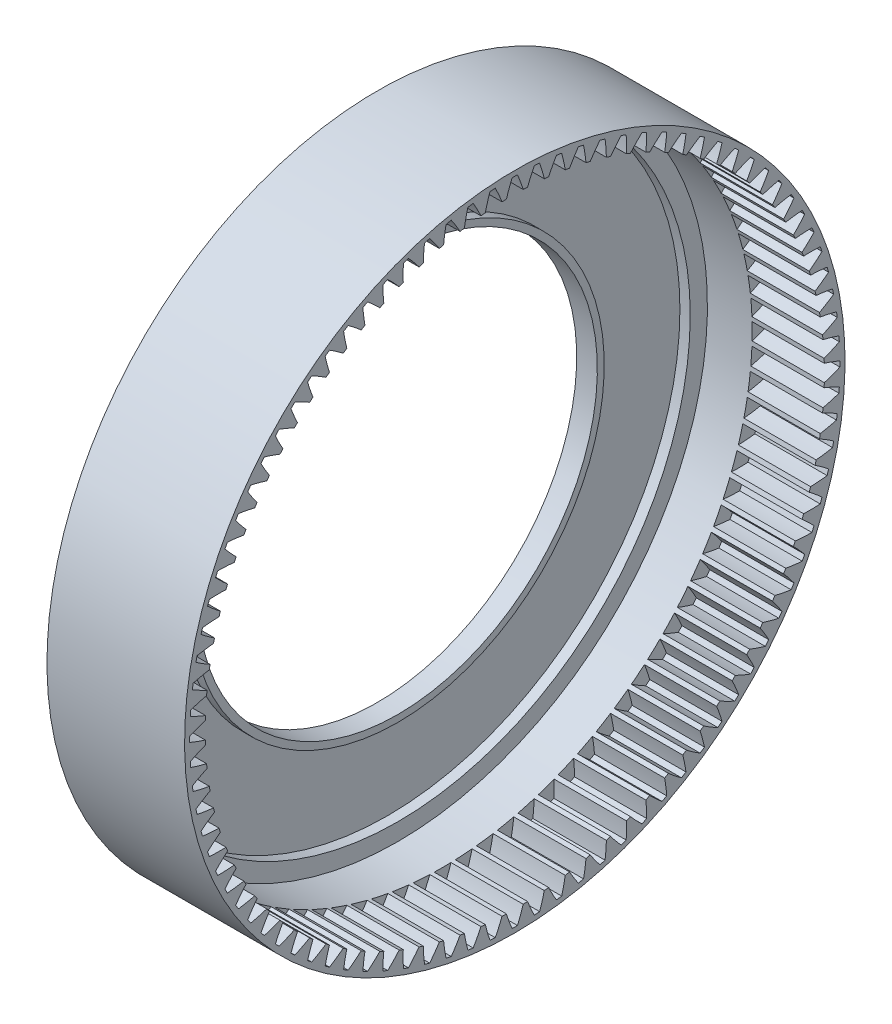
SolidWorks part; units mm, degrees
ref_plane "Front Plane" through (0, 0, 0) normal (0, 0, 1) x (1, 0, 0)
ref_plane "Top Plane" through (0, 0, 0) normal (0, 1, 0) x (1, 0, 0)
ref_plane "Right Plane" through (0, 0, 0) normal (1, 0, 0) x (0, 0, -1)
ref_plane "Plane1" through (0, 0, 0) normal (0, 0, -1) x (-1, 0, 0)
sketch "Sketch1" plane through (0, 0, 0) normal (0, 0, -1) x (-1, 0, 0)
  line L0 (-20, 48) -> (-20, 0)
  line L1 (-20, 0) -> (0, 0)
  line L2 (0, 0) -> (0, 48)
  line L3 (0, 48) -> (-20, 48)
  line L4 (-20, 0) -> (0, 0) construction
  dimension "D1" = 48
  dimension "D2" = 20
revolve "Revolve1" add sketch "Sketch1" angle 360 about L4 reverse direction yes
sketch "Sketch2" plane through (20, 0, 0) normal (1, 0, 0) x (0, 0, -1)
  arc A0 (-4.9202, -44.7302) -> (-4.2833, -44.7957) centre (0, 0) ccw
  arc A1 (-4.2833, -44.7957) -> (-3.6099, -47.1129) centre (18.1092, -39.5446) ccw
  arc A2 (-3.6099, -47.1129) -> (-2.8389, -47.1656) centre (0, 0) ccw
  arc A3 (-2.8389, -47.1656) -> (-1.8563, -44.9617) centre (-23.3252, -36.7104) ccw
  arc A4 (-1.8563, -44.9617) -> (-1.2163, -44.9836) centre (0, 0) ccw
  arc A5 (-1.2163, -44.9836) -> (-0.3864, -47.2494) centre (20.7656, -38.2166) ccw
  arc A6 (-0.3864, -47.2494) -> (0.3864, -47.2494) centre (0, 0) ccw
  arc A7 (0.3864, -47.2494) -> (1.2163, -44.9836) centre (-20.7656, -38.2166) ccw
  arc A8 (1.2163, -44.9836) -> (1.8563, -44.9617) centre (0, 0) ccw
  arc A9 (1.8563, -44.9617) -> (2.8389, -47.1656) centre (23.3252, -36.7104) ccw
  arc A10 (2.8389, -47.1656) -> (3.6099, -47.1129) centre (0, 0) ccw
  arc A11 (3.6099, -47.1129) -> (4.2833, -44.7957) centre (-18.1092, -39.5446) ccw
  arc A12 (4.2833, -44.7957) -> (4.9202, -44.7302) centre (0, 0) ccw
  arc A13 (4.9202, -44.7302) -> (6.051, -46.8619) centre (25.7761, -35.0331) ccw
  arc A14 (6.051, -46.8619) -> (6.8166, -46.7567) centre (0, 0) ccw
  arc A15 (6.8166, -46.7567) -> (7.3303, -44.399) centre (-15.3684, -40.6882) ccw
  arc A16 (7.3303, -44.399) -> (7.9613, -44.2902) centre (0, 0) ccw
  arc A17 (7.9613, -44.2902) -> (9.2349, -46.3398) centre (28.1067, -33.1924) ccw
  arc A18 (9.2349, -46.3398) -> (9.9915, -46.1825) centre (0, 0) ccw
  arc A19 (9.9915, -46.1825) -> (10.3431, -43.7952) centre (-12.5559, -41.6422) ccw
  arc A20 (10.3431, -43.7952) -> (10.9652, -43.6436) centre (0, 0) ccw
  arc A21 (10.9652, -43.6436) -> (12.3757, -45.6015) centre (30.3063, -31.1969) ccw
  arc A22 (12.3757, -45.6015) -> (13.1198, -45.393) centre (0, 0) ccw
  arc A23 (13.1198, -45.393) -> (13.3077, -42.9873) centre (-9.6849, -42.4019) ccw
  arc A24 (13.3077, -42.9873) -> (13.918, -42.7936) centre (0, 0) ccw
  arc A25 (13.918, -42.7936) -> (15.4588, -44.6507) centre (32.3646, -29.056) ccw
  arc A26 (15.4588, -44.6507) -> (16.1869, -44.3919) centre (0, 0) ccw
  arc A27 (16.1869, -44.3919) -> (16.2102, -41.9789) centre (-6.7687, -42.964) ccw
  arc A28 (16.2102, -41.9789) -> (16.8058, -41.744) centre (0, 0) ccw
  arc A29 (16.8058, -41.744) -> (18.4698, -43.4916) centre (34.272, -26.7796) ccw
  arc A30 (18.4698, -43.4916) -> (19.1786, -43.1838) centre (0, 0) ccw
  arc A31 (19.1786, -43.1838) -> (19.0371, -40.7748) centre (-3.821, -43.3257) ccw
  arc A32 (19.0371, -40.7748) -> (19.6154, -40.4998) centre (0, 0) ccw
  arc A33 (19.6154, -40.4998) -> (21.3948, -42.1298) centre (36.0196, -24.3784) ccw
  arc A34 (21.3948, -42.1298) -> (22.0809, -41.7743) centre (0, 0) ccw
  arc A35 (22.0809, -41.7743) -> (21.7753, -39.3806) centre (-0.8554, -43.4855) ccw
  arc A36 (21.7753, -39.3806) -> (22.3335, -39.0668) centre (0, 0) ccw
  arc A37 (22.3335, -39.0668) -> (24.2199, -40.5716) centre (37.5993, -21.8635) ccw
  arc A38 (24.2199, -40.5716) -> (24.8802, -40.1701) centre (0, 0) ccw
  arc A39 (24.8802, -40.1701) -> (24.412, -37.8028) centre (2.1142, -43.4425) ccw
  arc A40 (24.412, -37.8028) -> (24.9474, -37.4517) centre (0, 0) ccw
  arc A41 (24.9474, -37.4517) -> (26.9322, -38.8242) centre (39.0037, -19.2467) ccw
  arc A42 (26.9322, -38.8242) -> (27.5635, -38.3785) centre (0, 0) ccw
  arc A43 (27.5635, -38.3785) -> (26.9349, -36.0488) centre (5.0738, -43.1969) ccw
  arc A44 (26.9349, -36.0488) -> (27.445, -35.6619) centre (0, 0) ccw
  arc A45 (27.445, -35.6619) -> (29.5188, -36.8957) centre (40.2262, -16.5401) ccw
  arc A46 (29.5188, -36.8957) -> (30.1183, -36.4081) centre (0, 0) ccw
  arc A47 (30.1183, -36.4081) -> (29.3321, -34.1266) centre (8.0099, -42.75) ccw
  arc A48 (29.3321, -34.1266) -> (29.8147, -33.7058) centre (0, 0) ccw
  arc A49 (29.8147, -33.7058) -> (31.9679, -34.7953) centre (41.2611, -13.7564) ccw
  arc A50 (31.9679, -34.7953) -> (32.5326, -34.2679) centre (0, 0) ccw
  arc A51 (32.5326, -34.2679) -> (31.5926, -32.0454) centre (10.9086, -42.1037) ccw
  arc A52 (31.5926, -32.0454) -> (32.0454, -31.5926) centre (0, 0) ccw
  arc A53 (32.0454, -31.5926) -> (34.2679, -32.5326) centre (42.1037, -10.9086) ccw
  arc A54 (34.2679, -32.5326) -> (34.7953, -31.9679) centre (0, 0) ccw
  arc A55 (34.7953, -31.9679) -> (33.7058, -29.8147) centre (13.7564, -41.2611) ccw
  arc A56 (33.7058, -29.8147) -> (34.1266, -29.3321) centre (0, 0) ccw
  arc A57 (34.1266, -29.3321) -> (36.4081, -30.1183) centre (42.75, -8.0099) ccw
  arc A58 (36.4081, -30.1183) -> (36.8957, -29.5188) centre (0, 0) ccw
  arc A59 (36.8957, -29.5188) -> (35.6619, -27.445) centre (16.5401, -40.2262) ccw
  arc A60 (35.6619, -27.445) -> (36.0488, -26.9349) centre (0, 0) ccw
  arc A61 (36.0488, -26.9349) -> (38.3785, -27.5635) centre (43.1969, -5.0738) ccw
  arc A62 (38.3785, -27.5635) -> (38.8242, -26.9322) centre (0, 0) ccw
  arc A63 (38.8242, -26.9322) -> (37.4517, -24.9474) centre (19.2467, -39.0037) ccw
  arc A64 (37.4517, -24.9474) -> (37.8028, -24.412) centre (0, 0) ccw
  arc A65 (37.8028, -24.412) -> (40.1701, -24.8802) centre (43.4425, -2.1142) ccw
  arc A66 (40.1701, -24.8802) -> (40.5716, -24.2199) centre (0, 0) ccw
  arc A67 (40.5716, -24.2199) -> (39.0668, -22.3335) centre (21.8635, -37.5993) ccw
  arc A68 (39.0668, -22.3335) -> (39.3806, -21.7753) centre (0, 0) ccw
  arc A69 (39.3806, -21.7753) -> (41.7743, -22.0809) centre (43.4855, 0.8554) ccw
  arc A70 (41.7743, -22.0809) -> (42.1298, -21.3948) centre (0, 0) ccw
  arc A71 (42.1298, -21.3948) -> (40.4998, -19.6154) centre (24.3784, -36.0196) ccw
  arc A72 (40.4998, -19.6154) -> (40.7748, -19.0371) centre (0, 0) ccw
  arc A73 (40.7748, -19.0371) -> (43.1838, -19.1786) centre (43.3257, 3.821) ccw
  arc A74 (43.1838, -19.1786) -> (43.4916, -18.4698) centre (0, 0) ccw
  arc A75 (43.4916, -18.4698) -> (41.744, -16.8058) centre (26.7796, -34.272) ccw
  arc A76 (41.744, -16.8058) -> (41.9789, -16.2102) centre (0, 0) ccw
  arc A77 (41.9789, -16.2102) -> (44.3919, -16.1869) centre (42.964, 6.7687) ccw
  arc A78 (44.3919, -16.1869) -> (44.6507, -15.4588) centre (0, 0) ccw
  arc A79 (44.6507, -15.4588) -> (42.7936, -13.918) centre (29.056, -32.3646) ccw
  arc A80 (42.7936, -13.918) -> (42.9873, -13.3077) centre (0, 0) ccw
  arc A81 (42.9873, -13.3077) -> (45.393, -13.1198) centre (42.4019, 9.6849) ccw
  arc A82 (45.393, -13.1198) -> (45.6015, -12.3757) centre (0, 0) ccw
  arc A83 (45.6015, -12.3757) -> (43.6436, -10.9652) centre (31.1969, -30.3063) ccw
  arc A84 (43.6436, -10.9652) -> (43.7952, -10.3431) centre (0, 0) ccw
  arc A85 (43.7952, -10.3431) -> (46.1825, -9.9915) centre (41.6422, 12.5559) ccw
  arc A86 (46.1825, -9.9915) -> (46.3398, -9.2349) centre (0, 0) ccw
  arc A87 (46.3398, -9.2349) -> (44.2902, -7.9613) centre (33.1924, -28.1067) ccw
  arc A88 (44.2902, -7.9613) -> (44.399, -7.3303) centre (0, 0) ccw
  arc A89 (44.399, -7.3303) -> (46.7567, -6.8166) centre (40.6882, 15.3684) ccw
  arc A90 (46.7567, -6.8166) -> (46.8619, -6.051) centre (0, 0) ccw
  arc A91 (46.8619, -6.051) -> (44.7302, -4.9202) centre (35.0331, -25.7761) ccw
  arc A92 (44.7302, -4.9202) -> (44.7957, -4.2833) centre (0, 0) ccw
  arc A93 (44.7957, -4.2833) -> (47.1129, -3.6099) centre (39.5446, 18.1092) ccw
  arc A94 (47.1129, -3.6099) -> (47.1656, -2.8389) centre (0, 0) ccw
  arc A95 (47.1656, -2.8389) -> (44.9617, -1.8563) centre (36.7104, -23.3252) ccw
  arc A96 (44.9617, -1.8563) -> (44.9836, -1.2163) centre (0, 0) ccw
  arc A97 (44.9836, -1.2163) -> (47.2494, -0.3864) centre (38.2166, 20.7656) ccw
  arc A98 (47.2494, -0.3864) -> (47.2494, 0.3864) centre (0, 0) ccw
  arc A99 (47.2494, 0.3864) -> (44.9836, 1.2163) centre (38.2166, -20.7656) ccw
  arc A100 (44.9836, 1.2163) -> (44.9617, 1.8563) centre (0, 0) ccw
  arc A101 (44.9617, 1.8563) -> (47.1656, 2.8389) centre (36.7104, 23.3252) ccw
  arc A102 (47.1656, 2.8389) -> (47.1129, 3.6099) centre (0, 0) ccw
  arc A103 (47.1129, 3.6099) -> (44.7957, 4.2833) centre (39.5446, -18.1092) ccw
  arc A104 (44.7957, 4.2833) -> (44.7302, 4.9202) centre (0, 0) ccw
  arc A105 (44.7302, 4.9202) -> (46.8619, 6.051) centre (35.0331, 25.7761) ccw
  arc A106 (46.8619, 6.051) -> (46.7567, 6.8166) centre (0, 0) ccw
  arc A107 (46.7567, 6.8166) -> (44.399, 7.3303) centre (40.6882, -15.3684) ccw
  arc A108 (44.399, 7.3303) -> (44.2902, 7.9613) centre (0, 0) ccw
  arc A109 (44.2902, 7.9613) -> (46.3398, 9.2349) centre (33.1924, 28.1067) ccw
  arc A110 (46.3398, 9.2349) -> (46.1825, 9.9915) centre (0, 0) ccw
  arc A111 (46.1825, 9.9915) -> (43.7952, 10.3431) centre (41.6422, -12.5559) ccw
  arc A112 (43.7952, 10.3431) -> (43.6436, 10.9652) centre (0, 0) ccw
  arc A113 (43.6436, 10.9652) -> (45.6015, 12.3757) centre (31.1969, 30.3063) ccw
  arc A114 (45.6015, 12.3757) -> (45.393, 13.1198) centre (0, 0) ccw
  arc A115 (45.393, 13.1198) -> (42.9873, 13.3077) centre (42.4019, -9.6849) ccw
  arc A116 (42.9873, 13.3077) -> (42.7936, 13.918) centre (0, 0) ccw
  arc A117 (42.7936, 13.918) -> (44.6507, 15.4588) centre (29.056, 32.3646) ccw
  arc A118 (44.6507, 15.4588) -> (44.3919, 16.1869) centre (0, 0) ccw
  arc A119 (44.3919, 16.1869) -> (41.9789, 16.2102) centre (42.964, -6.7687) ccw
  arc A120 (41.9789, 16.2102) -> (41.744, 16.8058) centre (0, 0) ccw
  arc A121 (41.744, 16.8058) -> (43.4916, 18.4698) centre (26.7796, 34.272) ccw
  arc A122 (43.4916, 18.4698) -> (43.1838, 19.1786) centre (0, 0) ccw
  arc A123 (43.1838, 19.1786) -> (40.7748, 19.0371) centre (43.3257, -3.821) ccw
  arc A124 (40.7748, 19.0371) -> (40.4998, 19.6154) centre (0, 0) ccw
  arc A125 (40.4998, 19.6154) -> (42.1298, 21.3948) centre (24.3784, 36.0196) ccw
  arc A126 (42.1298, 21.3948) -> (41.7743, 22.0809) centre (0, 0) ccw
  arc A127 (41.7743, 22.0809) -> (39.3806, 21.7753) centre (43.4855, -0.8554) ccw
  arc A128 (39.3806, 21.7753) -> (39.0668, 22.3335) centre (0, 0) ccw
  arc A129 (39.0668, 22.3335) -> (40.5716, 24.2199) centre (21.8635, 37.5993) ccw
  arc A130 (40.5716, 24.2199) -> (40.1701, 24.8802) centre (0, 0) ccw
  arc A131 (40.1701, 24.8802) -> (37.8028, 24.412) centre (43.4425, 2.1142) ccw
  arc A132 (37.8028, 24.412) -> (37.4517, 24.9474) centre (0, 0) ccw
  arc A133 (37.4517, 24.9474) -> (38.8242, 26.9322) centre (19.2467, 39.0037) ccw
  arc A134 (38.8242, 26.9322) -> (38.3785, 27.5635) centre (0, 0) ccw
  arc A135 (38.3785, 27.5635) -> (36.0488, 26.9349) centre (43.1969, 5.0738) ccw
  arc A136 (36.0488, 26.9349) -> (35.6619, 27.445) centre (0, 0) ccw
  arc A137 (35.6619, 27.445) -> (36.8957, 29.5188) centre (16.5401, 40.2262) ccw
  arc A138 (36.8957, 29.5188) -> (36.4081, 30.1183) centre (0, 0) ccw
  arc A139 (36.4081, 30.1183) -> (34.1266, 29.3321) centre (42.75, 8.0099) ccw
  arc A140 (34.1266, 29.3321) -> (33.7058, 29.8147) centre (0, 0) ccw
  arc A141 (33.7058, 29.8147) -> (34.7953, 31.9679) centre (13.7564, 41.2611) ccw
  arc A142 (34.7953, 31.9679) -> (34.2679, 32.5326) centre (0, 0) ccw
  arc A143 (34.2679, 32.5326) -> (32.0454, 31.5926) centre (42.1037, 10.9086) ccw
  arc A144 (32.0454, 31.5926) -> (31.5926, 32.0454) centre (0, 0) ccw
  arc A145 (31.5926, 32.0454) -> (32.5326, 34.2679) centre (10.9086, 42.1037) ccw
  arc A146 (32.5326, 34.2679) -> (31.9679, 34.7953) centre (0, 0) ccw
  arc A147 (31.9679, 34.7953) -> (29.8147, 33.7058) centre (41.2611, 13.7564) ccw
  arc A148 (29.8147, 33.7058) -> (29.3321, 34.1266) centre (0, 0) ccw
  arc A149 (29.3321, 34.1266) -> (30.1183, 36.4081) centre (8.0099, 42.75) ccw
  arc A150 (30.1183, 36.4081) -> (29.5188, 36.8957) centre (0, 0) ccw
  arc A151 (29.5188, 36.8957) -> (27.445, 35.6619) centre (40.2262, 16.5401) ccw
  arc A152 (27.445, 35.6619) -> (26.9349, 36.0488) centre (0, 0) ccw
  arc A153 (26.9349, 36.0488) -> (27.5635, 38.3785) centre (5.0738, 43.1969) ccw
  arc A154 (27.5635, 38.3785) -> (26.9322, 38.8242) centre (0, 0) ccw
  arc A155 (26.9322, 38.8242) -> (24.9474, 37.4517) centre (39.0037, 19.2467) ccw
  arc A156 (24.9474, 37.4517) -> (24.412, 37.8028) centre (0, 0) ccw
  arc A157 (24.412, 37.8028) -> (24.8802, 40.1701) centre (2.1142, 43.4425) ccw
  arc A158 (24.8802, 40.1701) -> (24.2199, 40.5716) centre (0, 0) ccw
  arc A159 (24.2199, 40.5716) -> (22.3335, 39.0668) centre (37.5993, 21.8635) ccw
  arc A160 (22.3335, 39.0668) -> (21.7753, 39.3806) centre (0, 0) ccw
  arc A161 (21.7753, 39.3806) -> (22.0809, 41.7743) centre (-0.8554, 43.4855) ccw
  arc A162 (22.0809, 41.7743) -> (21.3948, 42.1298) centre (0, 0) ccw
  arc A163 (21.3948, 42.1298) -> (19.6154, 40.4998) centre (36.0196, 24.3784) ccw
  arc A164 (19.6154, 40.4998) -> (19.0371, 40.7748) centre (0, 0) ccw
  arc A165 (19.0371, 40.7748) -> (19.1786, 43.1838) centre (-3.821, 43.3257) ccw
  arc A166 (19.1786, 43.1838) -> (18.4698, 43.4916) centre (0, 0) ccw
  arc A167 (18.4698, 43.4916) -> (16.8058, 41.744) centre (34.272, 26.7796) ccw
  arc A168 (16.8058, 41.744) -> (16.2102, 41.9789) centre (0, 0) ccw
  arc A169 (16.2102, 41.9789) -> (16.1869, 44.3919) centre (-6.7687, 42.964) ccw
  arc A170 (16.1869, 44.3919) -> (15.4588, 44.6507) centre (0, 0) ccw
  arc A171 (15.4588, 44.6507) -> (13.918, 42.7936) centre (32.3646, 29.056) ccw
  arc A172 (13.918, 42.7936) -> (13.3077, 42.9873) centre (0, 0) ccw
  arc A173 (13.3077, 42.9873) -> (13.1198, 45.393) centre (-9.6849, 42.4019) ccw
  arc A174 (13.1198, 45.393) -> (12.3757, 45.6015) centre (0, 0) ccw
  arc A175 (12.3757, 45.6015) -> (10.9652, 43.6436) centre (30.3063, 31.1969) ccw
  arc A176 (10.9652, 43.6436) -> (10.3431, 43.7952) centre (0, 0) ccw
  arc A177 (10.3431, 43.7952) -> (9.9915, 46.1825) centre (-12.5559, 41.6422) ccw
  arc A178 (9.9915, 46.1825) -> (9.2349, 46.3398) centre (0, 0) ccw
  arc A179 (9.2349, 46.3398) -> (7.9613, 44.2902) centre (28.1067, 33.1924) ccw
  arc A180 (7.9613, 44.2902) -> (7.3303, 44.399) centre (0, 0) ccw
  arc A181 (7.3303, 44.399) -> (6.8166, 46.7567) centre (-15.3684, 40.6882) ccw
  arc A182 (6.8166, 46.7567) -> (6.051, 46.8619) centre (0, 0) ccw
  arc A183 (6.051, 46.8619) -> (4.9202, 44.7302) centre (25.7761, 35.0331) ccw
  arc A184 (4.9202, 44.7302) -> (4.2833, 44.7957) centre (0, 0) ccw
  arc A185 (4.2833, 44.7957) -> (3.6099, 47.1129) centre (-18.1092, 39.5446) ccw
  arc A186 (3.6099, 47.1129) -> (2.8389, 47.1656) centre (0, 0) ccw
  arc A187 (2.8389, 47.1656) -> (1.8563, 44.9617) centre (23.3252, 36.7104) ccw
  arc A188 (1.8563, 44.9617) -> (1.2163, 44.9836) centre (0, 0) ccw
  arc A189 (1.2163, 44.9836) -> (0.3864, 47.2494) centre (-20.7656, 38.2166) ccw
  arc A190 (0.3864, 47.2494) -> (-0.3864, 47.2494) centre (0, 0) ccw
  arc A191 (-0.3864, 47.2494) -> (-1.2163, 44.9836) centre (20.7656, 38.2166) ccw
  arc A192 (-1.2163, 44.9836) -> (-1.8563, 44.9617) centre (0, 0) ccw
  arc A193 (-1.8563, 44.9617) -> (-2.8389, 47.1656) centre (-23.3252, 36.7104) ccw
  arc A194 (-2.8389, 47.1656) -> (-3.6099, 47.1129) centre (0, 0) ccw
  arc A195 (-3.6099, 47.1129) -> (-4.2833, 44.7957) centre (18.1092, 39.5446) ccw
  arc A196 (-4.2833, 44.7957) -> (-4.9202, 44.7302) centre (0, 0) ccw
  arc A197 (-4.9202, 44.7302) -> (-6.051, 46.8619) centre (-25.7761, 35.0331) ccw
  arc A198 (-6.051, 46.8619) -> (-6.8166, 46.7567) centre (0, 0) ccw
  arc A199 (-6.8166, 46.7567) -> (-7.3303, 44.399) centre (15.3684, 40.6882) ccw
  arc A200 (-7.3303, 44.399) -> (-7.9613, 44.2902) centre (0, 0) ccw
  arc A201 (-7.9613, 44.2902) -> (-9.2349, 46.3398) centre (-28.1067, 33.1924) ccw
  arc A202 (-9.2349, 46.3398) -> (-9.9915, 46.1825) centre (0, 0) ccw
  arc A203 (-9.9915, 46.1825) -> (-10.3431, 43.7952) centre (12.5559, 41.6422) ccw
  arc A204 (-10.3431, 43.7952) -> (-10.9652, 43.6436) centre (0, 0) ccw
  arc A205 (-10.9652, 43.6436) -> (-12.3757, 45.6015) centre (-30.3063, 31.1969) ccw
  arc A206 (-12.3757, 45.6015) -> (-13.1198, 45.393) centre (0, 0) ccw
  arc A207 (-13.1198, 45.393) -> (-13.3077, 42.9873) centre (9.6849, 42.4019) ccw
  arc A208 (-13.3077, 42.9873) -> (-13.918, 42.7936) centre (0, 0) ccw
  arc A209 (-13.918, 42.7936) -> (-15.4588, 44.6507) centre (-32.3646, 29.056) ccw
  arc A210 (-15.4588, 44.6507) -> (-16.1869, 44.3919) centre (0, 0) ccw
  arc A211 (-16.1869, 44.3919) -> (-16.2102, 41.9789) centre (6.7687, 42.964) ccw
  arc A212 (-16.2102, 41.9789) -> (-16.8058, 41.744) centre (0, 0) ccw
  arc A213 (-16.8058, 41.744) -> (-18.4698, 43.4916) centre (-34.272, 26.7796) ccw
  arc A214 (-18.4698, 43.4916) -> (-19.1786, 43.1838) centre (0, 0) ccw
  arc A215 (-19.1786, 43.1838) -> (-19.0371, 40.7748) centre (3.821, 43.3257) ccw
  arc A216 (-19.0371, 40.7748) -> (-19.6154, 40.4998) centre (0, 0) ccw
  arc A217 (-19.6154, 40.4998) -> (-21.3948, 42.1298) centre (-36.0196, 24.3784) ccw
  arc A218 (-21.3948, 42.1298) -> (-22.0809, 41.7743) centre (0, 0) ccw
  arc A219 (-22.0809, 41.7743) -> (-21.7753, 39.3806) centre (0.8554, 43.4855) ccw
  arc A220 (-21.7753, 39.3806) -> (-22.3335, 39.0668) centre (0, 0) ccw
  arc A221 (-22.3335, 39.0668) -> (-24.2199, 40.5716) centre (-37.5993, 21.8635) ccw
  arc A222 (-24.2199, 40.5716) -> (-24.8802, 40.1701) centre (0, 0) ccw
  arc A223 (-24.8802, 40.1701) -> (-24.412, 37.8028) centre (-2.1142, 43.4425) ccw
  arc A224 (-24.412, 37.8028) -> (-24.9474, 37.4517) centre (0, 0) ccw
  arc A225 (-24.9474, 37.4517) -> (-26.9322, 38.8242) centre (-39.0037, 19.2467) ccw
  arc A226 (-26.9322, 38.8242) -> (-27.5635, 38.3785) centre (0, 0) ccw
  arc A227 (-27.5635, 38.3785) -> (-26.9349, 36.0488) centre (-5.0738, 43.1969) ccw
  arc A228 (-26.9349, 36.0488) -> (-27.445, 35.6619) centre (0, 0) ccw
  arc A229 (-27.445, 35.6619) -> (-29.5188, 36.8957) centre (-40.2262, 16.5401) ccw
  arc A230 (-29.5188, 36.8957) -> (-30.1183, 36.4081) centre (0, 0) ccw
  arc A231 (-30.1183, 36.4081) -> (-29.3321, 34.1266) centre (-8.0099, 42.75) ccw
  arc A232 (-29.3321, 34.1266) -> (-29.8147, 33.7058) centre (0, 0) ccw
  arc A233 (-29.8147, 33.7058) -> (-31.9679, 34.7953) centre (-41.2611, 13.7564) ccw
  arc A234 (-31.9679, 34.7953) -> (-32.5326, 34.2679) centre (0, 0) ccw
  arc A235 (-32.5326, 34.2679) -> (-31.5926, 32.0454) centre (-10.9086, 42.1037) ccw
  arc A236 (-31.5926, 32.0454) -> (-32.0454, 31.5926) centre (0, 0) ccw
  arc A237 (-32.0454, 31.5926) -> (-34.2679, 32.5326) centre (-42.1037, 10.9086) ccw
  arc A238 (-34.2679, 32.5326) -> (-34.7953, 31.9679) centre (0, 0) ccw
  arc A239 (-34.7953, 31.9679) -> (-33.7058, 29.8147) centre (-13.7564, 41.2611) ccw
  arc A240 (-33.7058, 29.8147) -> (-34.1266, 29.3321) centre (0, 0) ccw
  arc A241 (-34.1266, 29.3321) -> (-36.4081, 30.1183) centre (-42.75, 8.0099) ccw
  arc A242 (-36.4081, 30.1183) -> (-36.8957, 29.5188) centre (0, 0) ccw
  arc A243 (-36.8957, 29.5188) -> (-35.6619, 27.445) centre (-16.5401, 40.2262) ccw
  arc A244 (-35.6619, 27.445) -> (-36.0488, 26.9349) centre (0, 0) ccw
  arc A245 (-36.0488, 26.9349) -> (-38.3785, 27.5635) centre (-43.1969, 5.0738) ccw
  arc A246 (-38.3785, 27.5635) -> (-38.8242, 26.9322) centre (0, 0) ccw
  arc A247 (-38.8242, 26.9322) -> (-37.4517, 24.9474) centre (-19.2467, 39.0037) ccw
  arc A248 (-37.4517, 24.9474) -> (-37.8028, 24.412) centre (0, 0) ccw
  arc A249 (-37.8028, 24.412) -> (-40.1701, 24.8802) centre (-43.4425, 2.1142) ccw
  arc A250 (-40.1701, 24.8802) -> (-40.5716, 24.2199) centre (0, 0) ccw
  arc A251 (-40.5716, 24.2199) -> (-39.0668, 22.3335) centre (-21.8635, 37.5993) ccw
  arc A252 (-39.0668, 22.3335) -> (-39.3806, 21.7753) centre (0, 0) ccw
  arc A253 (-39.3806, 21.7753) -> (-41.7743, 22.0809) centre (-43.4855, -0.8554) ccw
  arc A254 (-41.7743, 22.0809) -> (-42.1298, 21.3948) centre (0, 0) ccw
  arc A255 (-42.1298, 21.3948) -> (-40.4998, 19.6154) centre (-24.3784, 36.0196) ccw
  arc A256 (-40.4998, 19.6154) -> (-40.7748, 19.0371) centre (0, 0) ccw
  arc A257 (-40.7748, 19.0371) -> (-43.1838, 19.1786) centre (-43.3257, -3.821) ccw
  arc A258 (-43.1838, 19.1786) -> (-43.4916, 18.4698) centre (0, 0) ccw
  arc A259 (-43.4916, 18.4698) -> (-41.744, 16.8058) centre (-26.7796, 34.272) ccw
  arc A260 (-41.744, 16.8058) -> (-41.9789, 16.2102) centre (0, 0) ccw
  arc A261 (-41.9789, 16.2102) -> (-44.3919, 16.1869) centre (-42.964, -6.7687) ccw
  arc A262 (-44.3919, 16.1869) -> (-44.6507, 15.4588) centre (0, 0) ccw
  arc A263 (-44.6507, 15.4588) -> (-42.7936, 13.918) centre (-29.056, 32.3646) ccw
  arc A264 (-42.7936, 13.918) -> (-42.9873, 13.3077) centre (0, 0) ccw
  arc A265 (-42.9873, 13.3077) -> (-45.393, 13.1198) centre (-42.4019, -9.6849) ccw
  arc A266 (-45.393, 13.1198) -> (-45.6015, 12.3757) centre (0, 0) ccw
  arc A267 (-45.6015, 12.3757) -> (-43.6436, 10.9652) centre (-31.1969, 30.3063) ccw
  arc A268 (-43.6436, 10.9652) -> (-43.7952, 10.3431) centre (0, 0) ccw
  arc A269 (-43.7952, 10.3431) -> (-46.1825, 9.9915) centre (-41.6422, -12.5559) ccw
  arc A270 (-46.1825, 9.9915) -> (-46.3398, 9.2349) centre (0, 0) ccw
  arc A271 (-46.3398, 9.2349) -> (-44.2902, 7.9613) centre (-33.1924, 28.1067) ccw
  arc A272 (-44.2902, 7.9613) -> (-44.399, 7.3303) centre (0, 0) ccw
  arc A273 (-44.399, 7.3303) -> (-46.7567, 6.8166) centre (-40.6882, -15.3684) ccw
  arc A274 (-46.7567, 6.8166) -> (-46.8619, 6.051) centre (0, 0) ccw
  arc A275 (-46.8619, 6.051) -> (-44.7302, 4.9202) centre (-35.0331, 25.7761) ccw
  arc A276 (-44.7302, 4.9202) -> (-44.7957, 4.2833) centre (0, 0) ccw
  arc A277 (-44.7957, 4.2833) -> (-47.1129, 3.6099) centre (-39.5446, -18.1092) ccw
  arc A278 (-47.1129, 3.6099) -> (-47.1656, 2.8389) centre (0, 0) ccw
  arc A279 (-47.1656, 2.8389) -> (-44.9617, 1.8563) centre (-36.7104, 23.3252) ccw
  arc A280 (-44.9617, 1.8563) -> (-44.9836, 1.2163) centre (0, 0) ccw
  arc A281 (-44.9836, 1.2163) -> (-47.2494, 0.3864) centre (-38.2166, -20.7656) ccw
  arc A282 (-47.2494, 0.3864) -> (-47.2494, -0.3864) centre (0, 0) ccw
  arc A283 (-47.2494, -0.3864) -> (-44.9836, -1.2163) centre (-38.2166, 20.7656) ccw
  arc A284 (-44.9836, -1.2163) -> (-44.9617, -1.8563) centre (0, 0) ccw
  arc A285 (-44.9617, -1.8563) -> (-47.1656, -2.8389) centre (-36.7104, -23.3252) ccw
  arc A286 (-47.1656, -2.8389) -> (-47.1129, -3.6099) centre (0, 0) ccw
  arc A287 (-47.1129, -3.6099) -> (-44.7957, -4.2833) centre (-39.5446, 18.1092) ccw
  arc A288 (-44.7957, -4.2833) -> (-44.7302, -4.9202) centre (0, 0) ccw
  arc A289 (-44.7302, -4.9202) -> (-46.8619, -6.051) centre (-35.0331, -25.7761) ccw
  arc A290 (-46.8619, -6.051) -> (-46.7567, -6.8166) centre (0, 0) ccw
  arc A291 (-46.7567, -6.8166) -> (-44.399, -7.3303) centre (-40.6882, 15.3684) ccw
  arc A292 (-44.399, -7.3303) -> (-44.2902, -7.9613) centre (0, 0) ccw
  arc A293 (-44.2902, -7.9613) -> (-46.3398, -9.2349) centre (-33.1924, -28.1067) ccw
  arc A294 (-46.3398, -9.2349) -> (-46.1825, -9.9915) centre (0, 0) ccw
  arc A295 (-46.1825, -9.9915) -> (-43.7952, -10.3431) centre (-41.6422, 12.5559) ccw
  arc A296 (-43.7952, -10.3431) -> (-43.6436, -10.9652) centre (0, 0) ccw
  arc A297 (-43.6436, -10.9652) -> (-45.6015, -12.3757) centre (-31.1969, -30.3063) ccw
  arc A298 (-45.6015, -12.3757) -> (-45.393, -13.1198) centre (0, 0) ccw
  arc A299 (-45.393, -13.1198) -> (-42.9873, -13.3077) centre (-42.4019, 9.6849) ccw
  arc A300 (-42.9873, -13.3077) -> (-42.7936, -13.918) centre (0, 0) ccw
  arc A301 (-42.7936, -13.918) -> (-44.6507, -15.4588) centre (-29.056, -32.3646) ccw
  arc A302 (-44.6507, -15.4588) -> (-44.3919, -16.1869) centre (0, 0) ccw
  arc A303 (-44.3919, -16.1869) -> (-41.9789, -16.2102) centre (-42.964, 6.7687) ccw
  arc A304 (-41.9789, -16.2102) -> (-41.744, -16.8058) centre (0, 0) ccw
  arc A305 (-41.744, -16.8058) -> (-43.4916, -18.4698) centre (-26.7796, -34.272) ccw
  arc A306 (-43.4916, -18.4698) -> (-43.1838, -19.1786) centre (0, 0) ccw
  arc A307 (-43.1838, -19.1786) -> (-40.7748, -19.0371) centre (-43.3257, 3.821) ccw
  arc A308 (-40.7748, -19.0371) -> (-40.4998, -19.6154) centre (0, 0) ccw
  arc A309 (-40.4998, -19.6154) -> (-42.1298, -21.3948) centre (-24.3784, -36.0196) ccw
  arc A310 (-42.1298, -21.3948) -> (-41.7743, -22.0809) centre (0, 0) ccw
  arc A311 (-41.7743, -22.0809) -> (-39.3806, -21.7753) centre (-43.4855, 0.8554) ccw
  arc A312 (-39.3806, -21.7753) -> (-39.0668, -22.3335) centre (0, 0) ccw
  arc A313 (-39.0668, -22.3335) -> (-40.5716, -24.2199) centre (-21.8635, -37.5993) ccw
  arc A314 (-40.5716, -24.2199) -> (-40.1701, -24.8802) centre (0, 0) ccw
  arc A315 (-40.1701, -24.8802) -> (-37.8028, -24.412) centre (-43.4425, -2.1142) ccw
  arc A316 (-37.8028, -24.412) -> (-37.4517, -24.9474) centre (0, 0) ccw
  arc A317 (-37.4517, -24.9474) -> (-38.8242, -26.9322) centre (-19.2467, -39.0037) ccw
  arc A318 (-38.8242, -26.9322) -> (-38.3785, -27.5635) centre (0, 0) ccw
  arc A319 (-38.3785, -27.5635) -> (-36.0488, -26.9349) centre (-43.1969, -5.0738) ccw
  arc A320 (-36.0488, -26.9349) -> (-35.6619, -27.445) centre (0, 0) ccw
  arc A321 (-35.6619, -27.445) -> (-36.8957, -29.5188) centre (-16.5401, -40.2262) ccw
  arc A322 (-36.8957, -29.5188) -> (-36.4081, -30.1183) centre (0, 0) ccw
  arc A323 (-36.4081, -30.1183) -> (-34.1266, -29.3321) centre (-42.75, -8.0099) ccw
  arc A324 (-34.1266, -29.3321) -> (-33.7058, -29.8147) centre (0, 0) ccw
  arc A325 (-33.7058, -29.8147) -> (-34.7953, -31.9679) centre (-13.7564, -41.2611) ccw
  arc A326 (-34.7953, -31.9679) -> (-34.2679, -32.5326) centre (0, 0) ccw
  arc A327 (-34.2679, -32.5326) -> (-32.0454, -31.5926) centre (-42.1037, -10.9086) ccw
  arc A328 (-32.0454, -31.5926) -> (-31.5926, -32.0454) centre (0, 0) ccw
  arc A329 (-31.5926, -32.0454) -> (-32.5326, -34.2679) centre (-10.9086, -42.1037) ccw
  arc A330 (-32.5326, -34.2679) -> (-31.9679, -34.7953) centre (0, 0) ccw
  arc A331 (-31.9679, -34.7953) -> (-29.8147, -33.7058) centre (-41.2611, -13.7564) ccw
  arc A332 (-29.8147, -33.7058) -> (-29.3321, -34.1266) centre (0, 0) ccw
  arc A333 (-29.3321, -34.1266) -> (-30.1183, -36.4081) centre (-8.0099, -42.75) ccw
  arc A334 (-30.1183, -36.4081) -> (-29.5188, -36.8957) centre (0, 0) ccw
  arc A335 (-29.5188, -36.8957) -> (-27.445, -35.6619) centre (-40.2262, -16.5401) ccw
  arc A336 (-27.445, -35.6619) -> (-26.9349, -36.0488) centre (0, 0) ccw
  arc A337 (-26.9349, -36.0488) -> (-27.5635, -38.3785) centre (-5.0738, -43.1969) ccw
  arc A338 (-27.5635, -38.3785) -> (-26.9322, -38.8242) centre (0, 0) ccw
  arc A339 (-26.9322, -38.8242) -> (-24.9474, -37.4517) centre (-39.0037, -19.2467) ccw
  arc A340 (-24.9474, -37.4517) -> (-24.412, -37.8028) centre (0, 0) ccw
  arc A341 (-24.412, -37.8028) -> (-24.8802, -40.1701) centre (-2.1142, -43.4425) ccw
  arc A342 (-24.8802, -40.1701) -> (-24.2199, -40.5716) centre (0, 0) ccw
  arc A343 (-24.2199, -40.5716) -> (-22.3335, -39.0668) centre (-37.5993, -21.8635) ccw
  arc A344 (-22.3335, -39.0668) -> (-21.7753, -39.3806) centre (0, 0) ccw
  arc A345 (-21.7753, -39.3806) -> (-22.0809, -41.7743) centre (0.8554, -43.4855) ccw
  arc A346 (-22.0809, -41.7743) -> (-21.3948, -42.1298) centre (0, 0) ccw
  arc A347 (-21.3948, -42.1298) -> (-19.6154, -40.4998) centre (-36.0196, -24.3784) ccw
  arc A348 (-19.6154, -40.4998) -> (-19.0371, -40.7748) centre (0, 0) ccw
  arc A349 (-19.0371, -40.7748) -> (-19.1786, -43.1838) centre (3.821, -43.3257) ccw
  arc A350 (-19.1786, -43.1838) -> (-18.4698, -43.4916) centre (0, 0) ccw
  arc A351 (-18.4698, -43.4916) -> (-16.8058, -41.744) centre (-34.272, -26.7796) ccw
  arc A352 (-16.8058, -41.744) -> (-16.2102, -41.9789) centre (0, 0) ccw
  arc A353 (-16.2102, -41.9789) -> (-16.1869, -44.3919) centre (6.7687, -42.964) ccw
  arc A354 (-16.1869, -44.3919) -> (-15.4588, -44.6507) centre (0, 0) ccw
  arc A355 (-15.4588, -44.6507) -> (-13.918, -42.7936) centre (-32.3646, -29.056) ccw
  arc A356 (-13.918, -42.7936) -> (-13.3077, -42.9873) centre (0, 0) ccw
  arc A357 (-13.3077, -42.9873) -> (-13.1198, -45.393) centre (9.6849, -42.4019) ccw
  arc A358 (-13.1198, -45.393) -> (-12.3757, -45.6015) centre (0, 0) ccw
  arc A359 (-12.3757, -45.6015) -> (-10.9652, -43.6436) centre (-30.3063, -31.1969) ccw
  arc A360 (-10.9652, -43.6436) -> (-10.3431, -43.7952) centre (0, 0) ccw
  arc A361 (-10.3431, -43.7952) -> (-9.9915, -46.1825) centre (12.5559, -41.6422) ccw
  arc A362 (-9.9915, -46.1825) -> (-9.2349, -46.3398) centre (0, 0) ccw
  arc A363 (-9.2349, -46.3398) -> (-7.9613, -44.2902) centre (-28.1067, -33.1924) ccw
  arc A364 (-7.9613, -44.2902) -> (-7.3303, -44.399) centre (0, 0) ccw
  arc A365 (-7.3303, -44.399) -> (-6.8166, -46.7567) centre (15.3684, -40.6882) ccw
  arc A366 (-6.8166, -46.7567) -> (-6.051, -46.8619) centre (0, 0) ccw
  arc A367 (-6.051, -46.8619) -> (-4.9202, -44.7302) centre (-25.7761, -35.0331) ccw
  point P553 (0, 0)
extrude "Cut-Extrude1" cut sketch "Sketch2" against normal offset from surface (17 mm away) 3 up to face at (0, -48, 0)
hole_wizard "M52 Clearance Hole1" positions "Sketch4" profile "Sketch3" hole size "M52" standard "ANSI Metric"
sketch "Sketch4" plane through (0, 0, 0) normal (-1, 0, 0) x (0, 0, 1)
  point P0 (0, 0)
sketch "Sketch3" plane through (0, 0, 0) normal (0, 1, 0) x (0, 0, 1)
  line L0 (0, 0) -> (0, 20)
  line L1 (0, 20) -> (29, 20)
  line L2 (29, 20) -> (29, 0)
  line L5 (29, 0) -> (0, 0)
  line L11 (0, -6.35) -> (0, 107.95) construction
  dimension "Thru Hole Dia." = 58
  dimension "Thru Hole Depth" = 20
sketch "Sketch5" plane through (3, 0, 0) normal (-1, 0, 0) x (0, 0, 1)
  circle A0 centre (0, 0) radius 30
  circle A1 centre (0, 0) radius 42.5
  dimension "D1" = 60
  dimension "D2" = 85
extrude "Cut-Extrude3" cut sketch "Sketch5" along normal blind 1.5
sketch "Sketch7" plane through (3, 0, 0) normal (1, 0, 0) x (0, 0, -1)
  circle A0 centre (0, 0) radius 48
  circle A1 centre (0, 0) radius 45
  dimension "D1" = 90
  dimension "D2" = 96
extrude "Boss-Extrude2" add sketch "Sketch7" along normal blind 6.5
